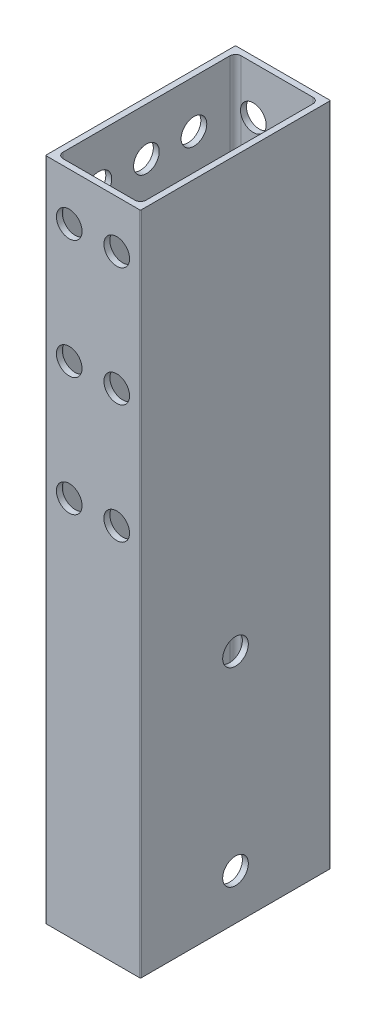
SolidWorks part; units mm, degrees
ref_plane "Front Plane" through (0, 0, 0) normal (0, 0, 1) x (1, 0, 0)
ref_plane "Top Plane" through (0, 0, 0) normal (0, 1, 0) x (1, 0, 0)
ref_plane "Right Plane" through (0, 0, 0) normal (1, 0, 0) x (0, 0, -1)
sketch "Sketch1" plane through (0, 0, 0) normal (0, 1, 0) x (1, 0, 0)
  line L0 (0.254, 50.8) -> (25.146, 50.8)
  line L1 (25.4, 50.546) -> (25.4, 0.254)
  line L2 (25.146, 0) -> (0.254, 0)
  line L3 (0, 0.254) -> (0, 50.546)
  line L4 (1.5875, 3.1115) -> (1.5875, 47.6885)
  line L5 (3.1115, 49.2125) -> (22.2885, 49.2125)
  line L6 (23.8125, 47.6885) -> (23.8125, 3.1115)
  line L7 (22.2885, 1.5875) -> (3.1115, 1.5875)
  line L8 (1.5875, 0.254) -> (1.5875, 50.546) construction
  line L9 (0.254, 49.2125) -> (25.146, 49.2125) construction
  line L10 (23.8125, 50.546) -> (23.8125, 0.254) construction
  line L11 (25.146, 1.5875) -> (0.254, 1.5875) construction
  arc A0 (0.254, 0) -> (0, 0.254) centre (0.254, 0.254) cw
  arc A1 (25.4, 0.254) -> (25.146, 0) centre (25.146, 0.254) cw
  arc A2 (25.146, 50.8) -> (25.4, 50.546) centre (25.146, 50.546) cw
  arc A3 (0.254, 50.8) -> (0, 50.546) centre (0.254, 50.546) ccw
  arc A4 (1.5875, 3.1115) -> (3.1115, 1.5875) centre (3.1115, 3.1115) ccw
  arc A5 (22.2885, 1.5875) -> (23.8125, 3.1115) centre (22.2885, 3.1115) ccw
  arc A6 (23.8125, 47.6885) -> (22.2885, 49.2125) centre (22.2885, 47.6885) ccw
  arc A7 (1.5875, 47.6885) -> (3.1115, 49.2125) centre (3.1115, 47.6885) cw
  point P8 (0, 0)
  point P11 (25.4, 0)
  point P14 (25.4, 50.8)
  point P17 (0, 50.8)
  dimension "D3" = 0.254
  dimension "D5" = 1.524
  dimension "D1" = 25.4
  dimension "D2" = 50.8
  dimension "D4" = 1.5875
extrude "Boss-Extrude1" add sketch "Sketch1" along normal blind 177.8
sketch "Sketch2" plane through (0, 0, 0) normal (-1, 0, 0) x (0, 0, 1)
  line L0 (-25.4, 0) -> (-25.4, 177.8) construction
  line L1 (-50.546, 0) -> (-0.254, 0) construction
  line L2 (-50.546, 177.8) -> (-0.254, 177.8) construction
  line L3 (-50.546, 177.8) -> (-50.546, 0) construction
  circle A0 centre (-25.4, 12.192) radius 10.16
  circle A1 centre (-25.4, 12.192) radius 3.429
  circle A2 centre (-25.4, 62.992) radius 10.16
  circle A3 centre (-25.4, 62.992) radius 3.429
  circle A4 centre (-38.1, 165.1) radius 3.429
  circle A5 centre (-25.4, 165.1) radius 3.429
  circle A6 centre (-12.7, 165.1) radius 3.429
  circle A7 centre (-25.4, 133.35) radius 3.429
  circle A8 centre (-12.7, 133.35) radius 3.429
  circle A9 centre (-25.4, 101.6) radius 3.429
  circle A10 centre (-12.7, 101.6) radius 3.429
  circle A11 centre (-38.1, 133.35) radius 3.429
  circle A12 centre (-38.1, 101.6) radius 3.429
  dimension "D1" = 20.32
  dimension "D2" = 6.858
  dimension "D6" = 12.446
  dimension "D3" = 12.192
  dimension "D5" = 50.8
  dimension "D7" = 12.7
  dimension "D10" = 31.75
  dimension "D11" = 12.7
  dimension "D4" = 2
  dimension "D8" = 3
  dimension "D9" = 3
extrude "Cut-Extrude1" cut sketch "Sketch2" against normal blind 12.7
extrude "Cut-Extrude2" cut sketch "Sketch2<3>" against normal through all contours L0 A3 | A3 L0 | L0 A1 | A1 L0 region at (0, 12.192, -26.8553) region at (0, 12.192, -23.9447) region at (0, 62.992, -26.8553) region at (0, 62.992, -23.9447)
sketch "Sketch2<3>" plane through (0, 0, 0) normal (-1, 0, 0) x (0, 0, 1) same geometry as "Sketch2"
sketch "Sketch3" plane through (0, 0, 0) normal (0, 0, 1) x (1, 0, 0)
  line L0 (25.146, 177.8) -> (25.146, 0) construction
  line L1 (0.254, 177.8) -> (25.146, 177.8) construction
  circle A0 centre (19.05, 165.1) radius 3.429
  circle A1 centre (6.35, 165.1) radius 3.429
  circle A2 centre (6.35, 133.35) radius 3.429
  circle A3 centre (6.35, 101.6) radius 3.429
  circle A4 centre (19.05, 133.35) radius 3.429
  circle A5 centre (19.05, 101.6) radius 3.429
  dimension "D1" = 6.858
  dimension "D2" = 6.096
  dimension "D3" = 12.7
  dimension "D6" = 12.7
  dimension "D7" = 31.75
  dimension "D4" = 2
  dimension "D5" = 3
extrude "Cut-Extrude3" cut sketch "Sketch3" against normal through all
